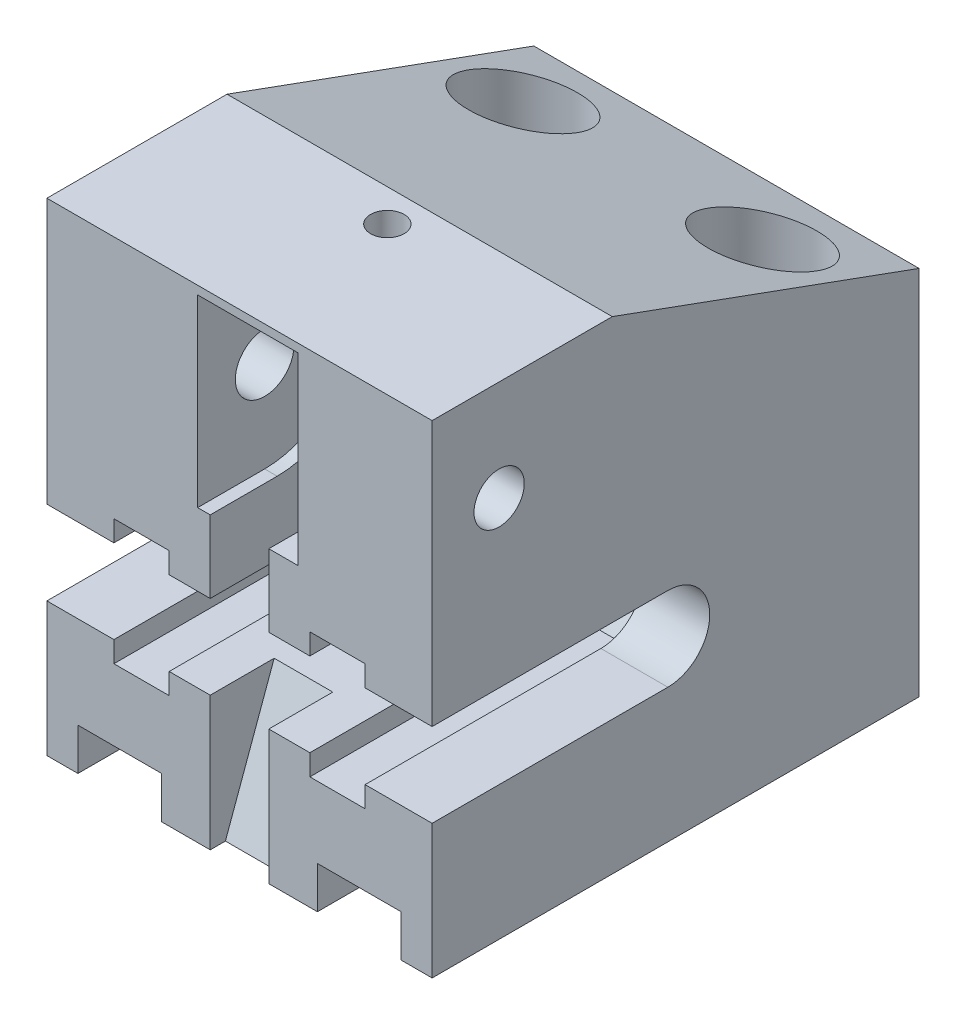
SolidWorks part; units mm, degrees
ref_plane "Top Plane" through (0, 0, 0) normal (0, 0, 1) x (1, 0, 0)
ref_plane "Right Plane" through (0, 0, 0) normal (0, 1, 0) x (1, 0, 0)
ref_plane "Front Plane" through (0, 0, 0) normal (1, 0, 0) x (0, 0, -1)
sketch "Sketch1" plane through (0, 0, 0) normal (0, 0, 1) x (1, 0, 0)
  line L0 (23, 10.5) -> (0, 10.5) construction
  line L1 (0, 0) -> (23, 0)
  line L2 (0, 0) -> (0, 32.5)
  line L4 (23, 0) -> (23, 32.5)
  line L7 (0, 32.5) -> (23, 32.5)
  line L9 (0, 8) -> (23, 8) construction
  line L10 (0, 10.5) -> (0, 0) construction
  line L11 (0, 0) -> (0, -11.5) construction
  line L12 (0, -11.5) -> (23, -11.5) construction
  line L13 (23, -11.5) -> (23, 32.5) construction
  dimension "D1" = 23
  dimension "D2" = 11.5
  dimension "D3" = 2.5
  dimension "D4" = 22
extrude "Boss-Extrude1" add sketch "Sketch1" along normal blind 18
sketch "Sketch2" plane through (0, 0, 0) normal (0, 0, -1) x (-1, 0, 0)
  line L0 (-23, 0) -> (-23, 32.5) construction
  line L1 (0, 0) -> (-23, 0)
  line L2 (0, 0) -> (0, 25)
  line L3 (0, 25) -> (-23, 25)
  line L4 (-23, 0) -> (-23, 25)
  dimension "D1" = 25
extrude "Boss-Extrude2" add sketch "Sketch2" along normal blind 15
chamfer "Chamfer1" distance 15 angle 45 1 edges at (11.5, 25, 0)
sketch "Sketch3" plane through (0, 0, 0) normal (0, -1, 0) x (1, 0, 0)
  line L0 (4.35, -10) -> (18.65, -10) construction
  line L3 (11.5, -15) -> (11.5, -10) construction
  line L4 (23, -15) -> (0, -15) construction
  circle A0 centre (4.35, -10) radius 1.8
  circle A1 centre (18.65, -10) radius 1.8
  dimension "D1" = 3.6
  dimension "D2" = 14.3
  dimension "D3" = 10
extrude "Cut-Extrude1" cut sketch "Sketch3" against normal through all
sketch "Sketch4" plane through (0, 0, 0) normal (-1, 0, 0) x (0, 0, 1)
  line L0 (0, 13) -> (18, 13)
  line L1 (18, 32.5) -> (18, 0) construction
  line L2 (18, 13) -> (18, 8)
  line L3 (18, 8) -> (0, 8)
  line L4 (0, 0) -> (0, 32.5) construction
  arc A0 (0, 13) -> (0, 8) centre (0, 10.5) ccw
  arc A1 (0, 8) -> (0, 13) centre (0, 10.5) ccw construction
  dimension "D1" = 5
extrude "Cut-Extrude2" cut sketch "Sketch4" against normal through all
sketch "Sketch5" plane through (0, 0, 0) normal (-1, 0, 0) x (0, 0, 1)
  line L0 (4.3301, 10.5) -> (2.1651, 14.25) construction
  line L1 (2.1651, 14.25) -> (-2.1651, 14.25)
  line L2 (-2.1651, 14.25) -> (-4.3301, 10.5)
  line L3 (-4.3301, 10.5) -> (-2.1651, 6.75)
  line L4 (-2.1651, 6.75) -> (2.1651, 6.75)
  line L5 (2.1651, 6.75) -> (4.3301, 10.5) construction
  line L6 (2.1651, 14.25) -> (18, 14.25)
  line L7 (18, 32.5) -> (18, 13) construction
  line L8 (18, 14.25) -> (18, 6.75)
  line L9 (18, 8) -> (18, 0) construction
  line L10 (18, 6.75) -> (2.1651, 6.75)
  circle A0 centre (0, 10.5) radius 4.3301 construction
  arc A1 (0, 13) -> (0, 8) centre (0, 10.5) ccw construction
  dimension "D1" = 7.5
extrude "Cut-Extrude3" cut sketch "Sketch5" against normal blind 3.3 from offset 4 offset against normal yes
ref_plane "Plane1" through (11.5, 0, 0) normal (-1, 0, 0) x (0, 0, 1)
sketch "Sketch7" plane through (0, 0, -15) normal (0, 0, -1) x (-1, 0, 0)
  line L0 (-23, 0) -> (0, 0) construction
  line L1 (-1.85, 0) -> (-6.85, 0)
  line L2 (-1.85, 0) -> (-1.85, 2.5)
  line L3 (-1.85, 2.5) -> (-6.85, 2.5)
  line L4 (-6.85, 0) -> (-6.85, 2.5)
  line L7 (-6.15, 0) -> (-2.55, 0) construction
  line L8 (-6.15, 0) -> (-2.55, 0) construction
  point P11 (-4.35, 0)
  point P12 (-4.35, 0)
  dimension "D1" = 5
  dimension "D2" = 2.5
extrude "Cut-Extrude4" cut sketch "Sketch7" against normal through all
sketch "Sketch8" plane through (0, 0, 0) normal (0, -1, 0) x (1, 0, 0)
  circle A0 centre (4.35, -10) radius 3.25
  dimension "D1" = 6.5
extrude "Cut-Extrude5" cut sketch "Sketch8" against normal through all from offset 6.5 offset against normal yes
mirror "Mirror1" about plane through (11.5, 0, 0) normal (-1, 0, 0) of "Cut-Extrude5", "Cut-Extrude4", "Cut-Extrude3"
sketch "Sketch9" plane through (0, 32.5, 0) normal (0, 1, 0) x (1, 0, 0)
  line L0 (23, -18) -> (0, 7.5) construction
  circle A0 centre (11.5, -5.25) radius 1
  dimension "D1" = 2
extrude "Cut-Extrude6" cut sketch "Sketch9" against normal blind 8
sketch "Sketch10" plane through (11.5, 0, 0) normal (-1, 0, 0) x (0, 0, 1)
  line L0 (5.25, 24.5) -> (18, 2.4164) construction
  line L1 (5.25, 24.5) -> (4.25, 24.5)
  line L2 (4.25, 24.5) -> (18, -13.2778)
  line L3 (18, -13.2778) -> (18, 2.4164) construction
  line L4 (6.25, 24.5) -> (4.25, 24.5)
  line L5 (4.25, 32.5) -> (4.25, 24.5) construction
  line L6 (6.25, 24.5) -> (6.25, 32.5) construction
  line L7 (6.25, 24.5) -> (4.25, 24.5) construction
  line L8 (18, 13) -> (18, 14.25) construction
  line L9 (18, 0) -> (18, 2.5) construction
  line L10 (6.25, 24.5) -> (31.3302, -4.978) construction
  line L11 (31.3302, -4.978) -> (18, -13.2778)
  line L12 (13.2797, -0.3089) -> (22.7203, 5.1416) construction
  line L13 (18, 2.4164) -> (24.6651, -9.1279) construction
  line L14 (6.25, 24.5) -> (56.7972, 10.8786)
  line L15 (56.7972, 10.8786) -> (31.3302, -4.978)
  dimension "D1" = 60
  dimension "D2" = 10
  dimension "D3" = 30
extrude "Cut-Extrude8" cut sketch "Sketch10" against normal mid plane 3.5 contours L11 L10 L4 L1 L2 region at (11.5, 7.5549, 26.2906)
sketch "Sketch11" plane through (11.5, 0, 0) normal (-1, 0, 0) x (0, 0, 1)
  line L0 (1.0296, 24.138) -> (5.2939, 23.3861)
  line L1 (5.2939, 23.3861) -> (6.7749, 19.3171)
  line L2 (6.7749, 19.3171) -> (3.9916, 16)
  line L3 (3.9916, 16) -> (-0.2728, 16.7519) construction
  line L4 (-0.2728, 16.7519) -> (-1.7537, 20.8209) construction
  line L5 (-1.7537, 20.8209) -> (1.0296, 24.138) construction
  line L6 (4.25, 24.5) -> (8.4357, 13) construction
  line L7 (-15, 0) -> (-15, 2.5) construction
  line L8 (-15, 9.0876) -> (-15, 18.3037)
  line L9 (-15, 18.3037) -> (-17.962, 17.2256) construction
  line L11 (0, 13) -> (18, 13) construction
  line L12 (1.0296, 24.138) -> (-15, 18.3037)
  line L13 (-17.962, 17.2256) -> (-15, 9.0876) construction
  line L14 (-15, 9.0876) -> (3.9916, 16)
  circle A0 centre (2.5106, 20.069) radius 4.3301 construction
  dimension "D1" = 7.5
  dimension "D2" = 0.6
  dimension "D3" = 3
extrude "Cut-Extrude7" cut sketch "Sketch11" against normal mid plane 3.5
sketch "Sketch12" plane through (11.5, 0, 0) normal (-1, 0, 0) x (0, 0, 1)
  line L0 (0.2028, 23.4857) -> (1.5709, 19.727)
  line L1 (1.5709, 19.727) -> (-16.481, 13.1566)
  line L2 (-16.481, 13.1566) -> (-17.8491, 16.9154)
  line L3 (-17.8491, 16.9154) -> (0.2028, 23.4857)
  line L4 (1.0296, 24.138) -> (3.9916, 16) construction
  line L5 (1.5709, 19.727) -> (2.5106, 20.069) construction
  line L6 (-15.1129, 9.3978) -> (-15, 9.0876) construction
  line L7 (-16.481, 13.1566) -> (-15.1129, 9.3978) construction
  dimension "D1" = 4
  dimension "D2" = 1
revolve "Cut-Revolve2" cut sketch "Sketch12" angle 360 about L1
ref_axis "Axis1" through (11.5, 14.7464, -12.1132) along (0, 0.342, 0.9397)
ref_plane "Plane2" through (0, -3.7579, -10.3246) normal (0, 0.342, 0.9397) x (1, 0, 0)
sketch "Sketch13" plane through (0, -3.7579, -10.3246) normal (0, 0.342, 0.9397) x (1, 0, 0)
  line L0 (18.65, 18) -> (11.5, 18) construction
  line L1 (18.65, 31.611) -> (18.65, 18) construction
  line L2 (11.5, 14.85) -> (11.5, -14.85) construction
  line L3 (18.65, 21.25) -> (11.5, 21.25)
  line L5 (18.65, 14.75) -> (11.5, 14.75)
  line L6 (11.5, 21.25) -> (11.5, 14.75)
  arc A1 (18.65, 14.75) -> (18.65, 21.25) centre (18.65, 18) ccw
  arc A2 (18.65, 21.25) -> (15.4, 18) centre (18.65, 18) ccw construction
  arc A3 (15.4, 18) -> (18.65, 14.75) centre (18.65, 18) ccw construction
  ellipse E0 centre (18.65, 31.611) end of major axis (15.4, 31.611) minor radius 1.9424 construction
  ellipse E1 centre (18.65, 31.611) end of major axis (21.9, 31.611) minor radius 1.9424 construction
  dimension "D1" = 6.5
extrude "Cut-Extrude9" cut sketch "Sketch13" along normal blind 13
sketch "Sketch15" plane through (0, 0.6884, 1.8914) normal (0, -0.342, -0.9397) x (-1, 0, 0)
  circle A0 centre (-18.65, 18) radius 1.35
  arc A1 (-18.65, 21.25) -> (-18.65, 14.75) centre (-18.65, 18) ccw construction
  dimension "D1" = 2.7
extrude "Cut-Extrude10" cut sketch "Sketch15" against normal blind 6
mirror "Mirror2" about plane through (11.5, 0, 0) normal (-1, 0, 0) of "Cut-Extrude10", "Cut-Extrude9"
sketch "Sketch16" plane through (11.5, 0, 0) normal (-1, 0, 0) x (0, 0, 1)
  line L0 (1.0296, 24.138) -> (3.9916, 16) construction
  line L1 (10.0751, 22.8223) -> (2.5106, 20.069) construction
  line L2 (6.3296, 18.7863) -> (4.6117, 23.5064) construction
  line L3 (10.0751, 28.3223) -> (25.5751, 28.3223)
  line L4 (25.5751, 28.3223) -> (25.5751, 17.3223)
  line L5 (25.5751, 17.3223) -> (10.0751, 17.3223)
  circle A0 centre (10.0751, 22.8223) radius 4 construction
  arc A1 (10.0751, 28.3223) -> (10.0751, 17.3223) centre (10.0751, 22.8223) ccw
  arc A2 (10.0751, 17.3223) -> (10.0751, 28.3223) centre (10.0751, 22.8223) ccw construction
  dimension "D1" = 8
  dimension "D2" = 0.9
  dimension "D3" = 11
  dimension "D4" = 10
extrude "Cut-Extrude11" cut sketch "Sketch16" against normal blind 3.5 and the other way blind 2.5
sketch "Sketch17" plane through (0, 0, 0) normal (-1, 0, 0) x (0, 0, 1)
  circle A0 centre (10.0751, 22.8223) radius 1.75
  arc A1 (10.0751, 28.3223) -> (10.0751, 17.3223) centre (10.0751, 22.8223) ccw construction
  dimension "D1" = 3.5
extrude "Cut-Extrude12" cut sketch "Sketch17" against normal up to surface (9 mm away) up to face at (9, 22.8223, 12.6626)
sketch "Sketch18" plane through (0, 0, 0) normal (-1, 0, 0) x (0, 0, 1)
  circle A0 centre (10.0751, 22.8223) radius 3
  dimension "D1" = 6
extrude "Cut-Extrude13" cut sketch "Sketch18" against normal blind 3
sketch "Sketch19" plane through (0, 0, 0) normal (-1, 0, 0) x (0, 0, 1)
  circle A0 centre (10.0751, 22.8223) radius 1.5
  dimension "D1" = 3
extrude "Cut-Extrude14" cut sketch "Sketch19" against normal through all
sketch "Sketch20" plane through (0, 0, 0) normal (0, -1, 0) x (1, 0, 0)
  line L0 (11.5, 5) -> (11.5, 13.1673) construction
  line L1 (13.25, 13.1673) -> (9.75, 13.1673) construction
  line L2 (13.25, 18) -> (16.15, 18) construction
  circle A0 centre (11.5, 5) radius 1.75
  dimension "D1" = 3.5
  dimension "D2" = 13
extrude "Cut-Extrude15" cut sketch "Sketch20" against normal up to surface (8 mm away) up to face at (11.5, 8, 11.5639)
sketch "Sketch21" plane through (0, 0, 0) normal (0, -1, 0) x (1, 0, 0)
  circle A0 centre (11.5, 5) radius 3
  dimension "D1" = 6
extrude "Cut-Extrude16" cut sketch "Sketch21" against normal blind 3
sketch "Sketch22" plane through (0, 0, 0) normal (0, -1, 0) x (1, 0, 0)
  circle A0 centre (11.5, 5) radius 1.5
  dimension "D1" = 3
extrude "Cut-Extrude17" cut sketch "Sketch22" against normal blind 17
sketch "Sketch23" plane through (0, 0, 0) normal (1, 0, 0) x (0, 0, -1)
  line L1 (-18, 32.5) -> (-14.0751, 32.5)
  line L2 (-18, 32.5) -> (-18, 0)
  line L3 (-18, 0) -> (-14.0751, 0)
  line L4 (-14.0751, 28.8223) -> (-14.0751, 0)
  line L5 (15, 22.1542) -> (-3.3202, 28.8223)
  line L6 (15, 0) -> (15, 25) construction
  line L7 (-18, 32.5) -> (7.5, 32.5) construction
  line L8 (-13.4248, 32.5) -> (15, 32.5)
  line L9 (15, 32.5) -> (15, 22.1542)
  line L10 (15, 9.0876) -> (-3.9916, 16) construction
  line L11 (-3.3202, 28.8223) -> (-14.0751, 28.8223)
  line L12 (-14.0751, 32.5) -> (-13.4248, 32.5)
  line L13 (-3.3202, 28.8223) -> (-13.4248, 32.5) construction
  line L14 (-14.0751, 32.5) -> (-14.0751, 28.8223) construction
  circle A0 centre (-10.0751, 22.8223) radius 3 construction
  dimension "D1" = 1
  dimension "D2" = 5
  dimension "D3" = 3
extrude "Cut-Extrude18" cut sketch "Sketch23" along normal through all
